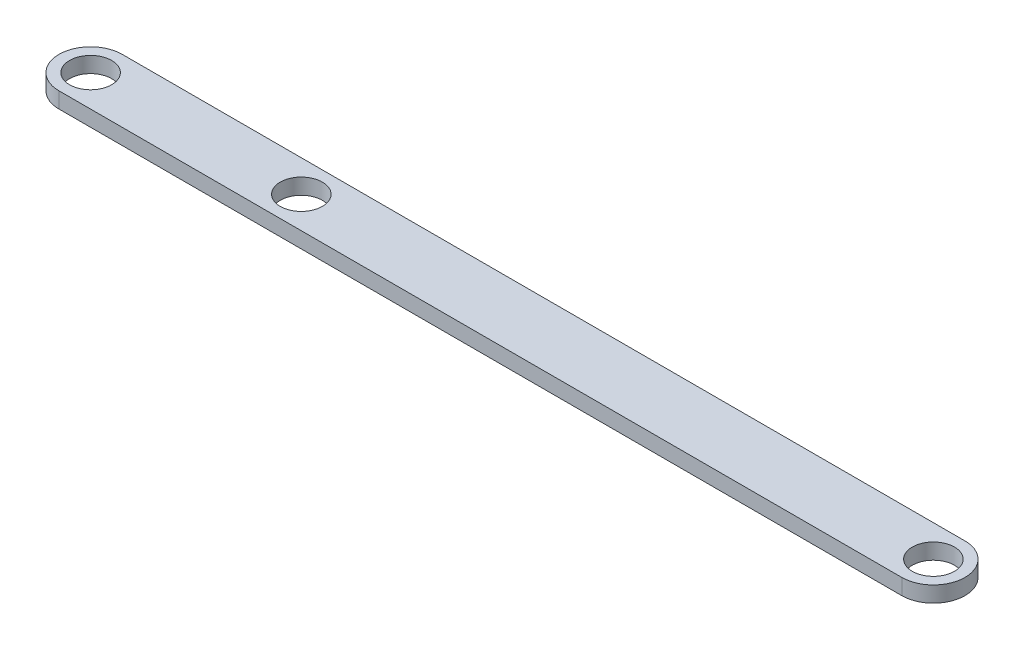
SolidWorks part; units mm, degrees
ref_plane "Front Plane" through (0, 0, 0) normal (0, 0, 1) x (1, 0, 0)
ref_plane "Top Plane" through (0, 0, 0) normal (0, 1, 0) x (1, 0, 0)
ref_plane "Right Plane" through (0, 0, 0) normal (1, 0, 0) x (0, 0, -1)
sketch "Sketch1" plane through (0, 0, 0) normal (0, 1, 0) x (1, 0, 0)
  line L0 (0, 6) -> (160, 6)
  line L1 (0, -6) -> (160, -6)
  circle A0 centre (0, 0) radius 4
  circle A1 centre (160, 0) radius 4
  arc A2 (0, 6) -> (0, -6) centre (0, 0) ccw
  arc A3 (160, -6) -> (160, 6) centre (160, 0) ccw
  circle A4 centre (0, 0) radius 6 construction
  circle A5 centre (160, 0) radius 6 construction
  dimension "D1" = 160
  dimension "D2" = 8
  dimension "D3" = 8
  dimension "D4" = 2
extrude "Boss-Extrude1" add sketch "Sketch1" along normal blind 3
sketch "Sketch2" plane through (0, 3, 0) normal (0, 1, 0) x (1, 0, 0)
  circle A0 centre (40, 0) radius 4
extrude "Cut-Extrude1" cut sketch "Sketch2" against normal through all
